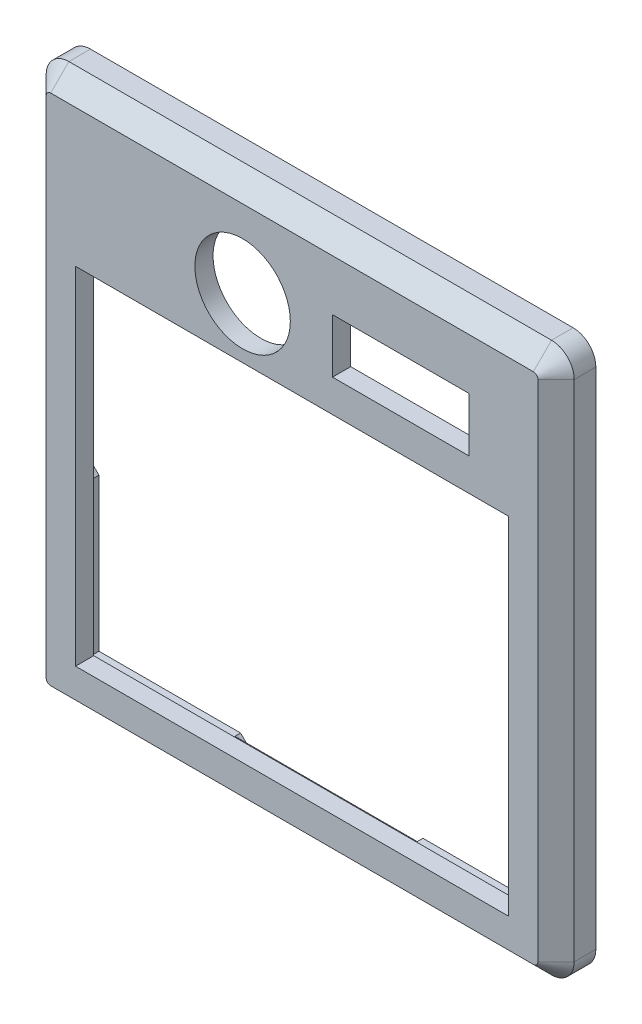
SolidWorks part; units mm, degrees
ref_plane "Front Plane" through (0, 0, 0) normal (1, 0, 0) x (0, 1, 0)
ref_plane "Top Plane" through (0, 0, 0) normal (0, 0, 1) x (0, 1, 0)
ref_plane "Right Plane" through (0, 0, 0) normal (0, 1, 0) x (-1, 0, 0)
sketch "Sketch1" plane through (0, 0, 0) normal (0, 0, 1) x (0, 1, 0)
  line L0 (39.3375, 50.0126) -> (39.3375, 10.8746) construction
  line L1 (-55.3847, -53.0098) -> (55.3847, -53.0098) construction
  line L2 (-55.3847, -53.0098) -> (-55.3847, 53.0098) construction
  line L3 (-55.3847, 53.0098) -> (55.3847, 53.0098) construction
  line L4 (55.3847, -53.0098) -> (55.3847, 53.0098) construction
  line L5 (-55.3847, -53.0098) -> (55.3847, 53.0098) construction
  line L6 (-55.3847, 53.0098) -> (55.3847, -53.0098) construction
  line L7 (-60.4647, -58.0898) -> (60.4647, -58.0898)
  line L8 (-60.4647, -58.0898) -> (-60.4647, 58.0898)
  line L9 (-60.4647, 58.0898) -> (60.4647, 58.0898)
  line L10 (60.4647, -58.0898) -> (60.4647, 58.0898)
  line L11 (-60.4647, -58.0898) -> (60.4647, 58.0898) construction
  line L12 (-60.4647, 58.0898) -> (60.4647, -58.0898) construction
  line L13 (-52.3875, -50.0126) -> (52.3875, -50.0126) construction
  line L14 (-52.3875, -50.0126) -> (-52.3875, 50.0126) construction
  line L15 (-52.3875, 50.0126) -> (52.3875, 50.0126) construction
  line L16 (52.3875, -50.0126) -> (52.3875, 50.0126) construction
  line L17 (-52.3875, -50.0126) -> (52.3875, 50.0126) construction
  line L18 (-52.3875, 50.0126) -> (52.3875, -50.0126) construction
  line L23 (39.3375, 10.8746) -> (39.3375, -8.9064) construction
  line L25 (33.3375, -8.9064) -> (45.2435, -8.9064)
  line L26 (33.3375, -8.9064) -> (33.3375, -38.9186)
  line L27 (33.3375, -38.9186) -> (45.2435, -38.9186)
  line L28 (45.2435, -8.9064) -> (45.2435, -38.9186)
  line L29 (-50.0063, 47.6313) -> (26.1935, 47.6313)
  line L30 (-50.0063, 47.6313) -> (-50.0063, -47.6314)
  line L31 (-50.0063, -47.6314) -> (26.1935, -47.6314)
  line L32 (26.1935, 47.6313) -> (26.1935, -47.6314)
  circle A0 centre (39.3375, 10.8746) radius 10.5
  point P0 (0, 0)
  point P6 (0, 0)
  point P11 (0, 0)
  dimension "D10" = 21
  dimension "D1" = 106.0196
  dimension "D2" = 110.7694
  dimension "D3" = 5.08
  dimension "D4" = 5.08
  dimension "D5" = 104.775
  dimension "D6" = 100.0252
  dimension "D7" = 2.3813
  dimension "D8" = 39.138
  dimension "D9" = 13.05
  dimension "D11" = 58.919
  dimension "D12" = 19.05
  dimension "D13" = 7.144
  dimension "D14" = 11.094
  dimension "D15" = 2.3813
  dimension "D16" = 2.3813
  dimension "D17" = 26.194
extrude "Boss-Extrude1" add sketch "Sketch1" along normal blind 4
sketch "Sketch2" plane through (0, 0, 0) normal (0, 0, -1) x (-1, 0, 0)
  line L1 (58.0898, -60.4647) -> (-58.0898, -60.4647)
  line L2 (58.0898, -60.4647) -> (58.0898, 60.4647)
  line L3 (58.0898, 60.4647) -> (-58.0898, 60.4647)
  line L4 (-58.0898, -60.4647) -> (-58.0898, 60.4647)
  line L5 (58.0898, -60.4647) -> (-58.0898, 60.4647) construction
  line L6 (58.0898, 60.4647) -> (-58.0898, -60.4647) construction
  line L7 (50.2688, -52.324) -> (-50.2688, -52.324) construction
  line L8 (50.2688, -52.324) -> (50.2688, 52.324) construction
  line L9 (50.2688, 52.324) -> (-50.2688, 52.324) construction
  line L10 (-50.2688, -52.324) -> (-50.2688, 52.324) construction
  line L11 (50.2688, -52.324) -> (-50.2688, 52.324) construction
  line L12 (50.2688, 52.324) -> (-50.2688, -52.324) construction
  line L13 (-51.2296, -53.324) -> (51.2296, -53.324)
  line L14 (-51.2296, -53.324) -> (-51.2296, 53.324)
  line L15 (-51.2296, 53.324) -> (51.2296, 53.324)
  line L16 (51.2296, -53.324) -> (51.2296, 53.324)
  line L17 (-51.2296, -53.324) -> (51.2296, 53.324) construction
  line L18 (-51.2296, 53.324) -> (51.2296, -53.324) construction
  point P0 (0, 0)
  point P7 (0, 0)
  point P12 (0, 0)
  dimension "D1" = 104.648
  dimension "D2" = 1
extrude "Boss-Extrude2" add sketch "Sketch2" along normal blind 4.75
sketch "Sketch4" plane through (0, 0, -4.75) normal (0, 0, -1) x (-1, 0, 0)
  line L0 (-50.0126, 0) -> (50.0126, 0) construction
  line L1 (-50.0126, -52.3875) -> (-21, -52.3875)
  line L2 (-50.0126, -52.3875) -> (-50.0126, -21)
  line L3 (-50.0126, 52.3875) -> (-21, 52.3875)
  line L4 (50.0126, -52.3875) -> (50.0126, -21)
  line L5 (-50.0126, -52.3875) -> (50.0126, 52.3875) construction
  line L6 (-50.0126, 52.3875) -> (50.0126, -52.3875) construction
  line L7 (0, 52.3875) -> (0, -52.3875) construction
  line L8 (50.0126, 0) -> (55.0126, 0) construction
  line L9 (55.0126, -16) -> (55.0126, 16)
  line L10 (50.0126, 21) -> (50.0126, 52.3875)
  line L11 (50.0126, -21) -> (50.0126, 21) construction
  line L12 (55.0126, 16) -> (50.0126, 21)
  line L13 (55.0126, -16) -> (50.0126, -21)
  line L14 (-21, -52.3875) -> (21, -52.3875) construction
  line L15 (21, -52.3875) -> (50.0126, -52.3875)
  line L16 (-50.0126, -21) -> (-50.0126, 21) construction
  line L17 (-50.0126, 21) -> (-50.0126, 52.3875)
  line L18 (-21, 52.3875) -> (21, 52.3875) construction
  line L19 (21, 52.3875) -> (50.0126, 52.3875)
  line L20 (0, 52.3875) -> (0, 57.3875) construction
  line L21 (-50.0126, 0) -> (-55.0126, 0) construction
  line L22 (0, -52.3875) -> (0, -57.3875) construction
  line L23 (-16, -57.3875) -> (16, -57.3875)
  line L24 (-55.0126, 16) -> (-55.0126, -16)
  line L25 (-16, 57.3875) -> (16, 57.3875)
  line L26 (16, 57.3875) -> (21, 52.3875)
  line L27 (-21, 52.3875) -> (-16, 57.3875)
  line L28 (-55.0126, 16) -> (-50.0126, 21)
  line L29 (-50.0126, -21) -> (-55.0126, -16)
  line L30 (-16, -57.3875) -> (-21, -52.3875)
  line L31 (16, -57.3875) -> (21, -52.3875)
  point P0 (0, 0)
  point P13 (55.0126, 0)
  point P31 (0, -57.3875)
  point P32 (-55.0126, 0)
  point P33 (0, 57.3875)
  dimension "D1" = 104.775
  dimension "D2" = 100.0252
  dimension "D3" = 5
  dimension "D4" = 32
  dimension "D5" = 135
  dimension "D6" = 135
  dimension "D7" = 135
  dimension "D8" = 135
extrude "Cut-Extrude1" cut sketch "Sketch4" against normal blind 1.25
sketch "Sketch6" plane through (0, 0, -3.5) normal (0, 0, -1) x (1, 0, 0)
  line L0 (0, 57.3875) -> (0, 56.3875) construction
  line L1 (16, 57.3875) -> (-16, 57.3875) construction
  line L2 (20.0635, 53.324) -> (-20.0635, 53.324) construction
  line L3 (-12.7, 54.324) -> (12.7, 54.324)
  line L4 (-12.7, 54.324) -> (-12.7, 56.3875)
  line L5 (-12.7, 56.3875) -> (12.7, 56.3875)
  line L6 (12.7, 54.324) -> (12.7, 56.3875)
  line L7 (-4.8125, 0) -> (4.8125, 0) construction
  line L8 (-12.7, -56.3875) -> (12.7, -56.3875)
  line L9 (12.7, -54.324) -> (12.7, -56.3875)
  line L10 (-12.7, -54.324) -> (12.7, -54.324)
  line L11 (-12.7, -54.324) -> (-12.7, -56.3875)
  line L12 (-55.0126, 0) -> (-54.0126, 0) construction
  line L13 (-55.0126, 16) -> (-55.0126, -16) construction
  line L14 (-51.2296, 19.783) -> (-51.2296, -19.783) construction
  line L15 (-54.0126, -12.7) -> (-52.2296, -12.7)
  line L16 (-54.0126, -12.7) -> (-54.0126, 12.7)
  line L17 (-54.0126, 12.7) -> (-52.2296, 12.7)
  line L18 (-52.2296, -12.7) -> (-52.2296, 12.7)
  line L19 (0, -4.8125) -> (0, 4.8125) construction
  line L20 (54.0126, 12.7) -> (52.2296, 12.7)
  line L21 (52.2296, -12.7) -> (52.2296, 12.7)
  line L22 (54.0126, -12.7) -> (52.2296, -12.7)
  line L23 (54.0126, -12.7) -> (54.0126, 12.7)
  point P9 (0, 56.3875)
  point P26 (-54.0126, 0)
  dimension "D1" = 1
  dimension "D2" = 1
  dimension "D3" = 25.4
  dimension "D4" = 1
  dimension "D5" = 1
  dimension "D6" = 25.4
extrude "Cut-Extrude2" cut sketch "Sketch6" against normal blind 2
sketch "Sketch7" plane through (-58.0898, 0, 0) normal (-1, 0, 0) x (0, -1, 0)
  line L1 (-43.0911, -1.7658) -> (-36.6903, -1.7658) construction
  line L2 (-44.3611, -3.0358) -> (-44.3611, -3.6454) construction
  line L3 (-43.0911, -4.9154) -> (-36.6903, -4.9154) construction
  line L4 (-35.4203, -3.0358) -> (-35.4203, -3.6454) construction
  line L5 (-60.4647, 4) -> (60.4647, 4) construction
  line L7 (-39.8907, -1.7658) -> (-39.8907, 1.2342) construction
  line L8 (-44.8211, 1.2342) -> (-34.9603, 1.2342)
  line L9 (-47.3611, -1.3058) -> (-47.3611, -5.3754)
  line L10 (-44.8211, -7.9154) -> (-34.9603, -7.9154)
  line L11 (-32.4203, -1.3058) -> (-32.4203, -5.3754)
  line L12 (-39.8907, -4.9154) -> (-39.8907, -7.9154) construction
  line L13 (-47.3611, -3.3406) -> (-44.3611, -3.3406) construction
  line L14 (-35.4203, -3.3406) -> (-32.4203, -3.3406) construction
  line L15 (-60.4647, 4) -> (-60.4647, -4.75) construction
  line L16 (60.4647, 4) -> (60.4647, -4.75) construction
  arc A0 (-36.6903, -4.9154) -> (-35.4203, -3.6454) centre (-36.6903, -3.6454) ccw construction
  arc A1 (-44.3611, -3.6454) -> (-43.0911, -4.9154) centre (-43.0911, -3.6454) ccw construction
  arc A2 (-43.0911, -1.7658) -> (-44.3611, -3.0358) centre (-43.0911, -3.0358) ccw construction
  arc A3 (-36.6903, -1.7658) -> (-35.4203, -3.0358) centre (-36.6903, -3.0358) cw construction
  arc A4 (-34.9603, -7.9154) -> (-32.4203, -5.3754) centre (-34.9603, -5.3754) ccw
  arc A5 (-34.9603, 1.2342) -> (-32.4203, -1.3058) centre (-34.9603, -1.3058) cw
  arc A6 (-44.8211, 1.2342) -> (-47.3611, -1.3058) centre (-44.8211, -1.3058) ccw
  arc A7 (-47.3611, -5.3754) -> (-44.8211, -7.9154) centre (-44.8211, -5.3754) ccw
  point P22 (-39.8907, 1.2342)
  point P23 (-39.8907, -1.7658)
  point P28 (-32.4203, -3.3406)
  point P29 (-35.4203, -3.3406)
  point P30 (-44.3611, -3.3406)
  point P31 (-47.3611, -3.3406)
  dimension "D5" = 1.27
  dimension "D8" = 2.54
  dimension "D1" = 3
  dimension "D2" = 16.1036
  dimension "D3" = 95.885
  dimension "D4" = 8.9154
  dimension "D6" = 5.7658
  dimension "D7" = 3
extrude "Cut-Extrude3" cut sketch "Sketch7" against normal blind 10.16
sketch "Sketch8" plane through (0, 0, -4.75) normal (0, 0, -1) x (1, 0, 0)
  line L0 (-58.0898, 60.4647) -> (-54.0258, 56.4007) construction
  line L2 (58.0898, 60.4647) -> (-58.0898, 60.4647) construction
  circle A0 centre (-54.0258, 56.4007) radius 1.3
  dimension "D2" = 2.6
  dimension "D1" = 45
  dimension "D3" = 4.064
extrude "Cut-Extrude4" cut sketch "Sketch8" against normal blind 4
mirror "Mirror1" about plane through (0, 0, 0) normal (1, 0, 0) of "Cut-Extrude4" second plane through (0, 0, 0) second plane normal (0, 1, 0)
fillet "Fillet1" radius 5 4 edges at (-58.0898, -60.4647, -0.375) (-58.0898, 60.4647, -0.375) (58.0898, -60.4647, -0.375) (58.0898, 60.4647, -0.375)
chamfer "Chamfer1" distance 4 angle 45 8 edges at (0, -60.4647, 4) (58.0898, 0, 4) (0, 60.4647, 4) (-58.0898, 0, 4) (56.6253, 59.0002, 4) (56.6253, -59.0002, 4) (-56.6253, 59.0002, 4) (-56.6253, -59.0002, 4)
